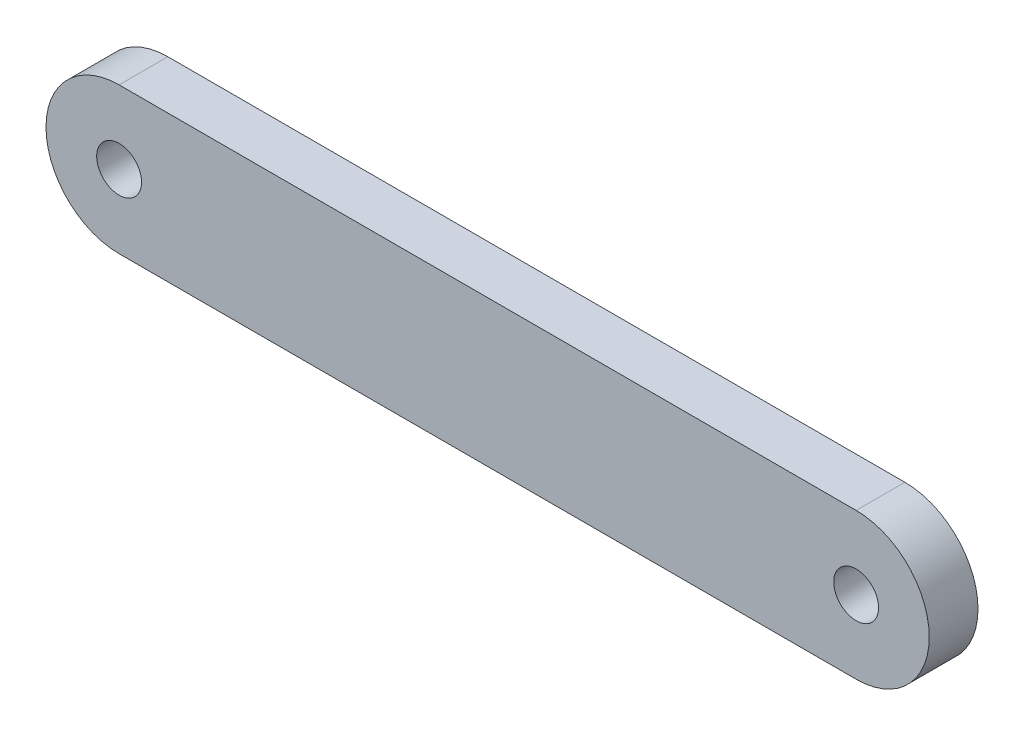
SolidWorks part; units mm, degrees
ref_plane "前视基准面" through (0, 0, 0) normal (0, 0, 1) x (1, 0, 0)
ref_plane "上视基准面" through (0, 0, 0) normal (0, 1, 0) x (1, 0, 0)
ref_plane "右视基准面" through (0, 0, 0) normal (1, 0, 0) x (0, 0, -1)
other "Configuration Table"
sketch "草图1" plane through (0, 0, 0) normal (0, 0, 1) x (1, 0, 0)
  line L1 (-37.8, 7.5) -> (37.8, 7.5)
  line L3 (-37.8, -7.5) -> (37.8, -7.5)
  line L5 (-37.8, 7.5) -> (37.8, -7.5) construction
  line L6 (-37.8, -7.5) -> (37.8, 7.5) construction
  arc A0 (-37.8, 7.5) -> (-37.8, -7.5) centre (-37.8, 0) ccw
  arc A1 (37.8, 7.5) -> (37.8, -7.5) centre (37.8, 0) cw
  circle A2 centre (-37.8, 0) radius 2.3
  circle A3 centre (37.8, 0) radius 2.3
  point P0 (0, 0)
  dimension "D1" = 4.6
  dimension "D2" = 4.6
  dimension "D3" = 75.6
  dimension "D4" = 15
extrude "凸台-拉伸1" add sketch "草图1" along normal blind 5
equation "\"fi\"=4.6"
equation "\"D1@草图1\"=\"fi\""
equation "\"D2@草图1\"=\"fi\""
equation "\"b0\"= 75.6'ground"
equation "\"D3@草图1\"=\"b0\""
equation "\"width\"=15"
equation "\"D4@草图1\"=\"width\""
equation "\"depth\"=5"
equation "\"D1@凸台-拉伸1\"=\"depth\""
equation "\"b1\"= \"b0\" *1.4/ 2'rocker"
equation "\"b2\"= \"b0\"'coupler"
equation "\"b3\"= \"b0\" / 2'coupler"
equation "\"b4\"= \"b0\" *2'leg"
equation "\"angle\"= 40*pi/180'ground水平夹角"
equation "\"b5\"=(\"b2\"^2+\"b4\"^2)^0.5'斜边"
